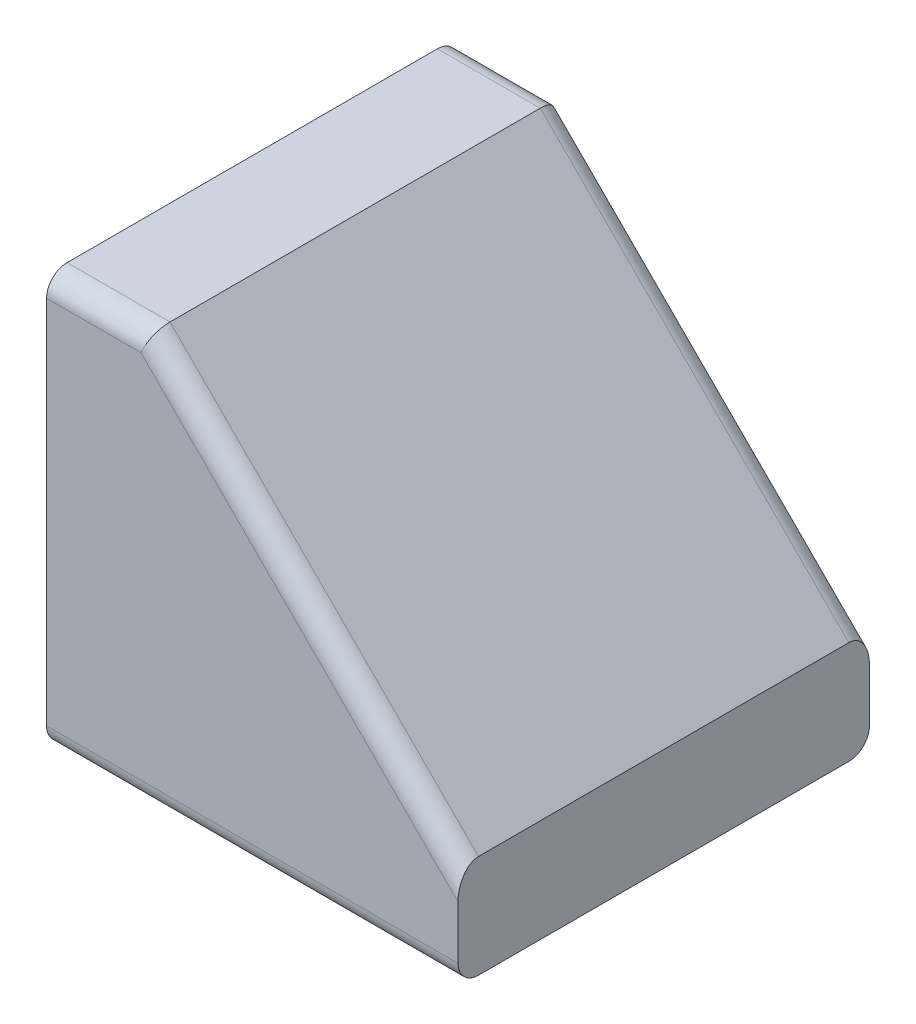
SolidWorks part; units mm, degrees
ref_plane "Front Plane" through (0, 0, 0) normal (0, 0, 1) x (1, 0, 0)
ref_plane "Top Plane" through (0, 0, 0) normal (0, 1, 0) x (1, 0, 0)
ref_plane "Right Plane" through (0, 0, 0) normal (1, 0, 0) x (0, 0, -1)
sketch "Sketch1" plane through (0, 0, 0) normal (0, 1, 0) x (1, 0, 0)
  line L1 (10, 10) -> (-10, 10)
  line L2 (10, 10) -> (10, -10)
  line L3 (10, -10) -> (-10, -10)
  line L4 (-10, 10) -> (-10, -10)
  line L5 (10, 10) -> (-10, -10) construction
  line L6 (10, -10) -> (-10, 10) construction
  point P0 (0, 0)
  dimension "D1" = 20
extrude "Boss-Extrude1" add sketch "Sketch1" along normal blind 20
chamfer "Chamfer1" distance 15 angle 45 1 edges at (10, 20, 0)
fillet "Fillet1" radius 1 6 edges at (2.5, 12.5, -10) (2.5, 12.5, 10) (0, 0, -10) (-7.5, 20, -10) (0, 0, 10) (-7.5, 20, 10)
sketch "Sketch2" plane through (-10, 0, 0) normal (-1, 0, 0) x (0, 0, 1)
  line L0 (-9, 20) -> (9, 20) construction
  circle A0 centre (0, 10) radius 2.05
  point P2 (0, 0)
  dimension "D1" = 4.1
  dimension "D2" = 10
extrude "Boss-Extrude2" add sketch "Sketch2" along normal blind 5
